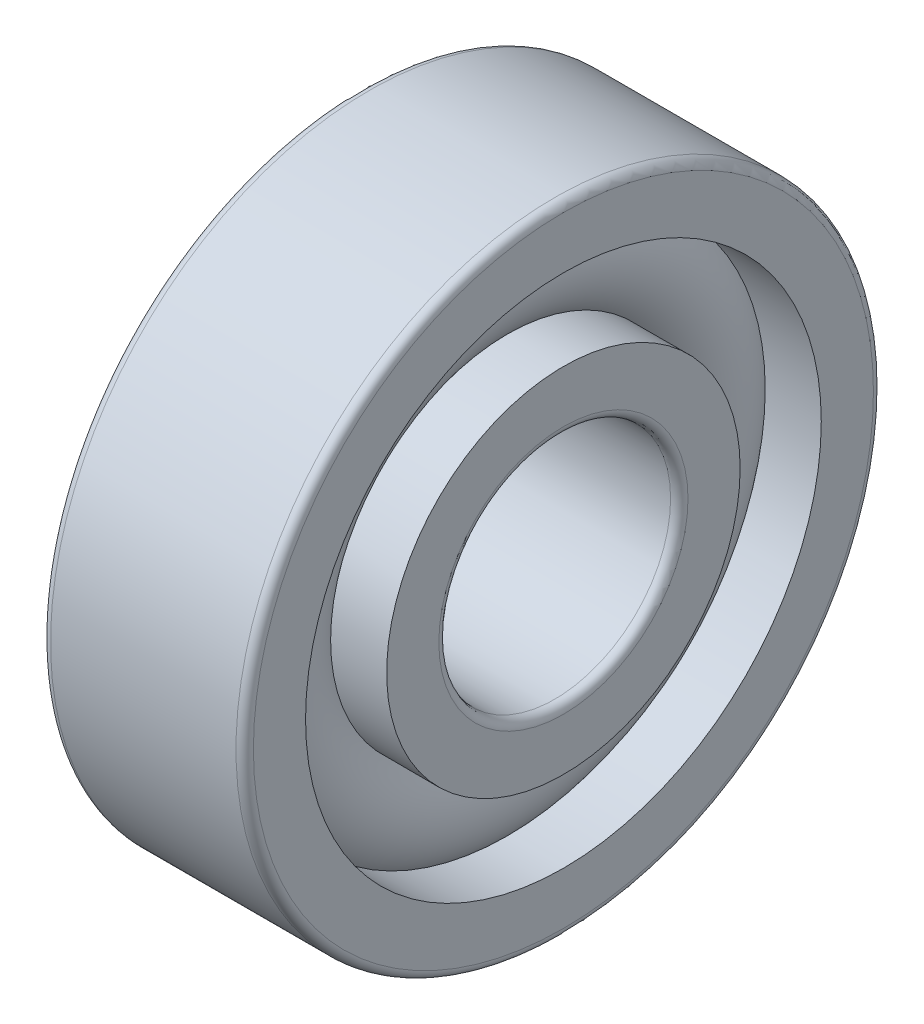
SolidWorks part; units mm, degrees
ref_plane "Plane1" through (0, 0, 0) normal (0, 0, 1) x (1, 0, 0)
ref_plane "Plane2" through (0, 0, 0) normal (0, 1, 0) x (1, 0, 0)
ref_plane "Plane3" through (0, 0, 0) normal (1, 0, 0) x (0, 0, -1)
sketch "Clipboard" plane through (0, 0, 0) normal (0, 0, 1) x (1, 0, 0)
  line L0 (-10, 0) -> (10, 0) construction
  line L1 (0, 0) -> (22.3471, -0.7804)
  line L2 (0, 0) -> (7.4954, 0.2617)
  line L3 (0, 0) -> (22.3471, -0.7804)
  line L4 (0, 0) -> (-22.3573, -0.3902)
  dimension "BallCLRad" = 7.5
sketch "CagSpiSke" plane through (0, 0, 0) normal (0, 0, 1) x (1, 0, 0)
  line L0 (0.21, 7.15) -> (0.21, 7.85)
  line L1 (0.21, 7.85) -> (-0.21, 7.85)
  line L2 (-0.21, 7.85) -> (-0.21, 7.15)
  line L3 (-0.21, 7.15) -> (0.21, 7.15)
  line L4 (-20.6375, 0) -> (20.6375, 0) construction
  line L5 (0, 0) -> (0, 23.7692) construction
  dimension "OD" = 15.7
  dimension "ID" = 14.3
revolve "CageSpine" add sketch "CagSpiSke" angle 0.001 about L4 reverse direction yes
ref_axis "Axis1" through (-50, 0, 0) along (1, 0, 0)
sketch "CagBalSke" plane through (0, 0, 0) normal (0, 0, 1) x (1, 0, 0)
  line L0 (-2.31, 7.5) -> (2.31, 7.5)
  line L1 (-1.905, 7.5) -> (1.905, 7.5) construction
  line L2 (-10, 0) -> (10, 0) construction
  line L3 (0, 0) -> (0, 24) construction
  arc A0 (2.31, 7.5) -> (-2.31, 7.5) centre (0, 7.5) cw
  dimension "BallCLRad" = 7.5
revolve "CageBall" [suppressed] add sketch "CagBalSke" angle 360 about L1 reverse direction yes
pattern_circular "CageBalls" [suppressed] count 2 every 180 about axis through (-50, 0, 0) along (1, 0, 0)
sketch "CagTrmODSke" plane through (0, 0, 0) normal (0, 0, 1) x (1, 0, 0)
  line L0 (2.311, 7.85) -> (2.311, 9.811)
  line L1 (2.311, 9.811) -> (-2.311, 9.811)
  line L2 (-2.311, 9.811) -> (-2.311, 7.85)
  line L3 (-2.311, 7.85) -> (2.311, 7.85)
  line L4 (-20.6375, 0) -> (20.6375, 0) construction
  line L5 (0, 0) -> (0, 25) construction
  dimension "Width" = 4.622
  dimension "ID" = 15.7
  dimension "OD" = 19.622
revolve "CageTrimOD" [suppressed] cut sketch "CagTrmODSke" angle 360 about L4 reverse direction yes
sketch "CagTrmIDSke" plane through (0, 0, 0) normal (0, 0, 1) x (1, 0, 0)
  line L0 (2.311, 5.191) -> (2.311, 7.15)
  line L1 (2.311, 7.15) -> (-2.311, 7.15)
  line L2 (-2.311, 7.15) -> (-2.311, 5.191)
  line L3 (-2.311, 5.191) -> (2.311, 5.191)
  line L4 (-20.6375, 0) -> (20.6375, 0) construction
  line L5 (0, 0) -> (0, 25) construction
  dimension "Width" = 4.622
  dimension "ID" = 10.382
  dimension "OD" = 14.3
revolve "CageTrimID" [suppressed] cut sketch "CagTrmIDSke" angle 360 about L4 reverse direction yes
sketch "BalSimSke" plane through (0, 0, 0) normal (0, 0, 1) x (1, 0, 0)
  line L0 (-10, 0) -> (10, 0) construction
  line L1 (-10, 7.5) -> (10, 7.5) construction
  line L2 (0, 0) -> (0, 23) construction
  circle A0 centre (0, 7.5) radius 2.1
  dimension "BallCLRad" = 7.5
  dimension "Ball_diameter" = 4.2
revolve "BallsSimplified" add sketch "BalSimSke" angle 360 about L0
sketch "BalDetSke" plane through (0, 0, 0) normal (0, 0, 1) x (1, 0, 0)
  line L0 (-2.1, 7.5) -> (2.1, 7.5)
  line L1 (-1.905, 7.5) -> (1.905, 7.5) construction
  line L2 (0, 0) -> (0, 25) construction
  arc A0 (2.1, 7.5) -> (-2.1, 7.5) centre (0, 7.5) cw
  dimension "BallCLRad" = 7.5
  dimension "Ball_diameter" = 4.2
revolve "BallDetailed" [suppressed] add sketch "BalDetSke" angle 360 about L1 reverse direction yes
sketch "InnRacSke" plane through (0, 0, 0) normal (0, 0, 1) x (1, 0, 0)
  line L0 (-1.5315, 6.1) -> (-3.5, 6.1)
  line L1 (-3.5, 6.1) -> (-3.5, 4.3)
  line L2 (-3.2, 4) -> (3.2, 4)
  line L3 (3.5, 4.3) -> (3.5, 6.1)
  line L4 (3.5, 6.1) -> (1.5315, 6.1)
  line L5 (-20.6375, 0) -> (20.6375, 0) construction
  line L6 (0, 0) -> (0, 30) construction
  arc A0 (-3.5, 4.3) -> (-3.2, 4) centre (-3.2, 4.3) ccw
  arc A1 (3.2, 4) -> (3.5, 4.3) centre (3.2, 4.3) ccw
  arc A2 (1.5315, 6.1) -> (-1.5315, 6.1) centre (0, 7.5) cw
  dimension "BallCLRad" = 7.5
  dimension "Fillet_radius" = 0.3
  dimension "Ball_diameter" = 4.15
  dimension "ID" = 8
  dimension "OD" = 12.2
  dimension "Width" = 7
revolve "InnerRace" add sketch "InnRacSke" angle 360 about L5 reverse direction yes
sketch "OutRacSke" plane through (0, 0, 0) normal (0, 0, 1) x (1, 0, 0)
  line L0 (-1.5315, 8.9) -> (-3.5, 8.9)
  line L1 (-3.5, 8.9) -> (-3.5, 10.7)
  line L2 (-3.2, 11) -> (3.2, 11)
  line L3 (3.5, 10.7) -> (3.5, 8.9)
  line L4 (3.5, 8.9) -> (1.5315, 8.9)
  line L5 (-20.6375, 0) -> (20.6375, 0) construction
  line L6 (0, 0) -> (0, 30) construction
  arc A0 (-3.5, 10.7) -> (-3.2, 11) centre (-3.2, 10.7) cw
  arc A1 (3.2, 11) -> (3.5, 10.7) centre (3.2, 10.7) cw
  arc A2 (1.5315, 8.9) -> (-1.5315, 8.9) centre (0, 7.5) ccw
  dimension "BallCLRad" = 7.5
  dimension "Fillet_radius" = 0.3
  dimension "Ball_diameter" = 4.15
  dimension "Width" = 7
revolve "OuterRace" add sketch "OutRacSke" angle 360 about L5 reverse direction yes
pattern_circular "BallsDetailed" [suppressed] count 2 every 180 about axis through (-50, 0, 0) along (1, 0, 0)
equation "\"BallCLRad@Clipboard\" = ( \"OD@OutRacSke\" + \"ID@InnRacSke\" ) / 4"
equation "\"BallCLRad@BalSimSke\" = \"BallCLRad@Clipboard\""
equation "\"BallCLRad@BalDetSke\" = \"BallCLRad@Clipboard\""
equation "\"BallCLRad@InnRacSke\" = \"BallCLRad@Clipboard\""
equation "\"BallCLRad@OutRacSke\" = \"BallCLRad@Clipboard\""
equation "\"Ball_diameter@InnRacSke\" = \"Ball_diameter@BalDetSke\" - 0.05"
equation "\"Ball_diameter@OutRacSke\" = \"Ball_diameter@BalDetSke\" - 0.05"
equation "\"Ball_diameter@BalSimSke\" = \"Ball_diameter@BalDetSke\""
equation "\"Width@OutRacSke\" = \"Width@InnRacSke\""
equation "\"Fillet_radius@OutRacSke\" = \"Fillet_radius@InnRacSke\""
equation "\"Max_count@Clipboard\" = int( 3.14159265 / atn(( \"Ball_diameter@BalDetSke\" / 2) / sqr( \"BallCLRad@Clipboard\"  *  \"BallCLRad@Clipboard\" - ( \"Ball_diameter@BalDetSke\" / 2) *  ( \"Ball_diameter@BalDetSke\" / 2))))"
equation "\"Max_count@Clipboard\" = ((sgn( \"Max_count@Clipboard\" - \"Count@Clipboard\" )-1)*( \"Max_count@Clipboard\" - \"Count@Clipboard\" ))/-2+ \"Count@Clipboard\""
equation "\"Count@BallsDetailed\" = int( \"Show_count@Clipboard\" ) "
equation "\"Count@BallsDetailed\" = ((sgn( \"Count@BallsDetailed\" - \"Max_count@Clipboard\" )-1)*( \"Count@BallsDetailed\" - \"Max_count@Clipboard\" ))/-2+ \"Max_count@Clipboard\""
equation "\"Count@BallsDetailed\" = ((sgn( \"Count@BallsDetailed\" - \"Min_count@Clipboard\" )+1)*( \"Count@BallsDetailed\" - \"Min_count@Clipboard\"))/2 +\"Min_count@Clipboard\""
equation "\"Angle@BallsDetailed\" = 360.0 / \"Max_count@Clipboard\""
equation "\"BallCLRad@CagBalSke\" = \"BallCLRad@Clipboard\""
equation "\"Count@CageBalls\" = \"Count@BallsDetailed\""
equation "\"Angle@CageBalls\" = \"Angle@BallsDetailed\""
equation "\"Angle@CageSpine\" =  \"Angle@CageBalls\" * ( \"Count@CageBalls\" -1 + int( \"Count@CageBalls\" / \"Max_count@Clipboard\" ) )  + 0.001 -  int( \"Count@CageBalls\" / \"Max_count@Clipboard\" ) * 0.001"
equation "\"Angle@CageSpine\" =  \"Angle@CageSpine\" * int( \"Min_count@Clipboard\" / 2) + int(1 / \"Min_count@Clipboard\")  * 0.001"
equation "\"CageWallOD@CagBalSke\" =  \"Ball_diameter@BalDetSke\" * 1.1"
equation "\"Thickness@CagSpiSke\" =  \"Ball_diameter@BalDetSke\" * 0.1"
equation "\"OD@CagTrmODSke\" = \"BallCLRad@Clipboard\" * 2 + \"CageWallOD@CagBalSke\" + 0.002"
equation "\"ID@CagTrmODSke\" = \"BallCLRad@Clipboard\" * 2 + \"Ball_diameter@BalDetSke\" / 6"
equation "\"OD@CagTrmIDSke\" = \"BallCLRad@Clipboard\" * 2 - \"Ball_diameter@BalDetSke\" / 6"
equation "\"ID@CagTrmIDSke\" = \"BallCLRad@Clipboard\" * 2 - \"CageWallOD@CagBalSke\" + 0.002"
equation "\"OD@CagSpiSke\" = \"ID@CagTrmODSke\""
equation "\"ID@CagSpiSke\" = \"OD@CagTrmIDSke\""
equation "\"Width@CagTrmODSke\" = \"CageWallOD@CagBalSke\" + 0.002"
equation "\"Width@CagTrmIDSke\" = \"CageWallOD@CagBalSke\" + 0.002"
